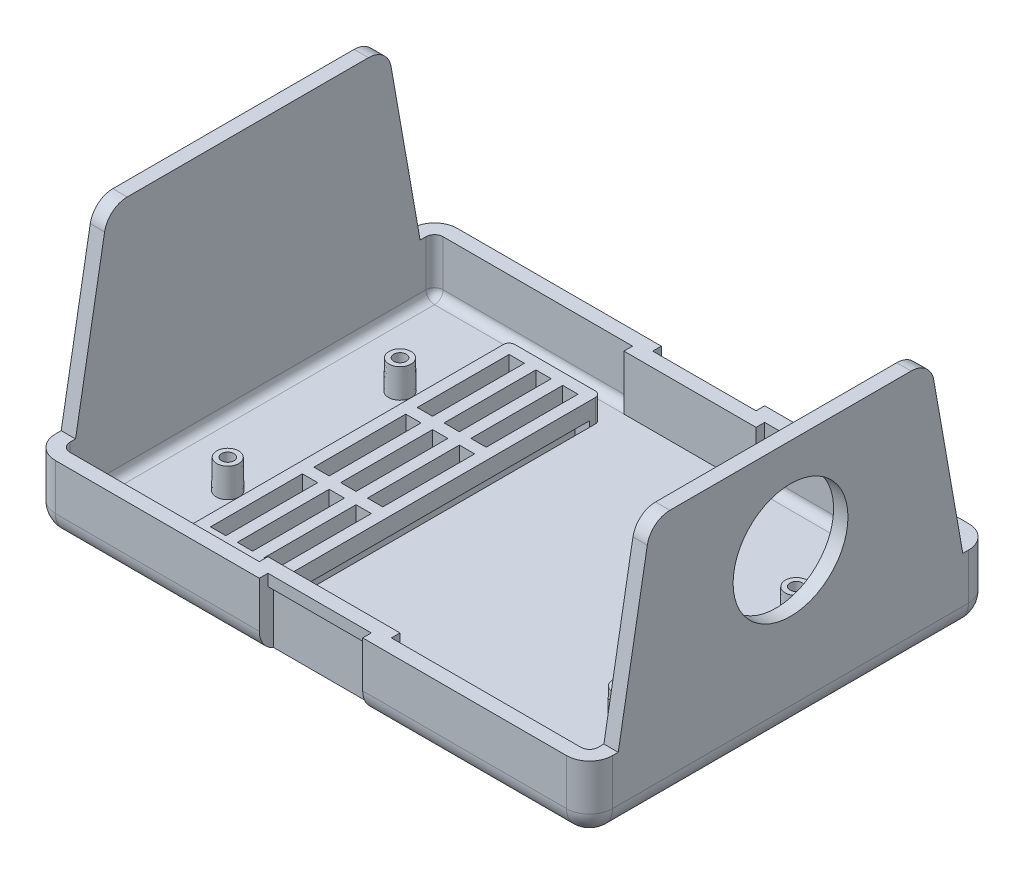
SolidWorks part; units mm, degrees
material "ABS"
ref_plane "Plano frontal" through (0, 0, 0) normal (0, 0, 1) x (1, 0, 0)
ref_plane "Plano superior" through (0, 0, 0) normal (0, 1, 0) x (1, 0, 0)
ref_plane "Plano direito" through (0, 0, 0) normal (1, 0, 0) x (0, 0, -1)
sketch "Esboço1" plane through (0, 0, 0) normal (0, 1, 0) x (1, 0, 0)
  line L0 (-48.5, 35) -> (48.5, -35) construction
  line L1 (-44.5, 35) -> (-9, 35)
  line L2 (-48.5, 31) -> (-48.5, -31)
  line L3 (-44.5, -35) -> (-9, -35)
  line L4 (48.5, 31) -> (48.5, -31)
  line L5 (9, 35) -> (44.5, 35)
  line L6 (9, -35) -> (44.5, -35)
  line L7 (-9, 35) -> (-9, 33.5)
  line L8 (-9, 33.5) -> (9, 33.5)
  line L9 (9, 35) -> (9, 33.5)
  line L11 (9, -35) -> (9, -33.5)
  line L12 (9, -33.5) -> (-9, -33.5)
  line L13 (-9, -35) -> (-9, -33.5)
  arc A0 (-48.5, -31) -> (-44.5, -35) centre (-44.5, -31) ccw
  arc A1 (44.5, -35) -> (48.5, -31) centre (44.5, -31) ccw
  arc A2 (44.5, 35) -> (48.5, 31) centre (44.5, 31) cw
  arc A3 (-44.5, 35) -> (-48.5, 31) centre (-44.5, 31) ccw
  point P7 (-48.5, -35)
  point P13 (48.5, 35)
  dimension "D3" = 4
  dimension "D1" = 97
  dimension "D2" = 70
  dimension "D4" = 1.5
  dimension "D5" = 1.5
  dimension "D6" = 18
  dimension "D7" = 18
  dimension "D8" = 9
  dimension "D9" = 9
extrude "Ressalto-extrusão1" add sketch "Esboço1" along normal blind 44
fillet "Filete1" radius 4 8 edges at (-47.3284, 0, 33.8284) (-48.5, 0, 0) (-47.3284, 0, -33.8284) (-26.75, 0, -35) (47.3284, 0, -33.8284) (48.5, 0, 0) (47.3284, 0, 33.8284) (-26.75, 0, 35)
shell "Casca1" thickness 2.5 removed face at (0, 44, 0)
sketch "Esboço2" plane through (0, 0, 0) normal (1, 0, 0) x (0, 0, -1)
  line L0 (-31, 44) -> (31, 44) construction
  line L1 (-21.0011, 44) -> (21.0011, 44)
  line L2 (-24.9404, 40.6946) -> (-30, 12)
  line L3 (-30, 12) -> (-42.6713, 12)
  line L4 (24.9404, 40.6946) -> (30, 12)
  line L5 (-42.6713, 12) -> (-42.6713, 55.4192)
  line L6 (-42.6713, 55.4192) -> (41.7141, 55.4192)
  line L7 (41.7141, 55.4192) -> (41.7141, 12)
  line L8 (41.7141, 12) -> (30, 12)
  arc A0 (21.0011, 44) -> (24.9404, 40.6946) centre (21.0011, 40) cw
  arc A1 (-21.0011, 44) -> (-24.9404, 40.6946) centre (-21.0011, 40) ccw
  dimension "D1" = 4
  dimension "D2" = 60
  dimension "D3" = 30
extrude "Corte-extrusão1" cut sketch "Esboço2" against normal mid plane 100
sketch "Esboço4" plane through (0, 2.5, 0) normal (0, 1, 0) x (1, 0, 0)
  line L0 (-44.5, 35) -> (-9, 35) construction
  line L1 (-9, -35) -> (-44.5, -35) construction
  line L2 (-48.5, 21.0011) -> (-48.5, -21.0011) construction
  line L3 (48.5, -21.0011) -> (48.5, 21.0011) construction
  circle A0 centre (-34.5, 15) radius 2
  circle A1 centre (-34.5, 15) radius 1
  circle A2 centre (-34.5, -15) radius 2
  circle A3 centre (-34.5, -15) radius 1
  circle A4 centre (34.5, 15) radius 2
  circle A5 centre (34.5, 15) radius 1
  circle A6 centre (34.5, -15) radius 2
  circle A7 centre (34.5, -15) radius 1
  dimension "D5" = 14
  dimension "D7" = 20
  dimension "D8" = 20
  dimension "D9" = 2
  dimension "D10" = 4
  dimension "D11" = 2
  dimension "D12" = 2
  dimension "D13" = 2
  dimension "D1" = 20
  dimension "D2" = 20
  dimension "D3" = 14
  dimension "D4" = 14
  dimension "D6" = 14
extrude "Ressalto-extrusão2" add sketch "Esboço4" along normal blind 5 draft 1 separate body
sketch "Esboço5" plane through (0, 2.5, 0) normal (0, 1, 0) x (1, 0, 0)
  line L0 (-48.5, 21.0011) -> (-48.5, -21.0011) construction
  line L1 (-27.5, -28) -> (-13.5, -28)
  line L2 (-28.5, -27) -> (-28.5, 27)
  line L3 (-27.5, 28) -> (-13.5, 28)
  line L4 (-12.5, -27) -> (-12.5, 27)
  line L6 (-26.5, 26) -> (-23.8333, 26)
  line L7 (-26.5, 26) -> (-26.5, 10)
  line L8 (-26.5, 10) -> (-23.8333, 10)
  line L9 (-23.8333, 26) -> (-23.8333, 10)
  line L10 (-21.8333, 26) -> (-19.1667, 26)
  line L11 (-21.8333, 26) -> (-21.8333, 10)
  line L12 (-21.8333, 10) -> (-19.1667, 10)
  line L13 (-19.1667, 26) -> (-19.1667, 10)
  line L14 (-17.1667, 26) -> (-14.5, 26)
  line L15 (-17.1667, 26) -> (-17.1667, 10)
  line L16 (-17.1667, 10) -> (-14.5, 10)
  line L17 (-14.5, 26) -> (-14.5, 10)
  line L18 (-26.5, 8) -> (-23.8333, 8)
  line L19 (-26.5, 8) -> (-26.5, -8)
  line L20 (-26.5, -8) -> (-23.8333, -8)
  line L21 (-23.8333, 8) -> (-23.8333, -8)
  line L22 (-21.8333, 8) -> (-19.1667, 8)
  line L23 (-21.8333, 8) -> (-21.8333, -8)
  line L24 (-21.8333, -8) -> (-19.1667, -8)
  line L25 (-19.1667, 8) -> (-19.1667, -8)
  line L26 (-17.1667, 8) -> (-14.5, 8)
  line L27 (-17.1667, 8) -> (-17.1667, -8)
  line L28 (-17.1667, -8) -> (-14.5, -8)
  line L29 (-14.5, 8) -> (-14.5, -8)
  line L30 (-26.5, -10) -> (-23.8333, -10)
  line L31 (-26.5, -10) -> (-26.5, -26)
  line L32 (-26.5, -26) -> (-23.8333, -26)
  line L33 (-23.8333, -10) -> (-23.8333, -26)
  line L34 (-21.8333, -10) -> (-19.1667, -10)
  line L35 (-21.8333, -10) -> (-21.8333, -26)
  line L36 (-21.8333, -26) -> (-19.1667, -26)
  line L37 (-19.1667, -10) -> (-19.1667, -26)
  line L38 (-17.1667, -10) -> (-14.5, -10)
  line L39 (-17.1667, -10) -> (-17.1667, -26)
  line L40 (-17.1667, -26) -> (-14.5, -26)
  line L41 (-14.5, -10) -> (-14.5, -26)
  arc A0 (-28.5, 27) -> (-27.5, 28) centre (-27.5, 27) cw
  arc A1 (-13.5, 28) -> (-12.5, 27) centre (-13.5, 27) cw
  arc A2 (-13.5, -28) -> (-12.5, -27) centre (-13.5, -27) ccw
  arc A3 (-27.5, -28) -> (-28.5, -27) centre (-27.5, -27) cw
  point P45 (-28.5, 28)
  point P50 (-12.5, -28)
  point P53 (-28.5, -28)
  dimension "D27" = 1
  dimension "D1" = 56
  dimension "D2" = 16
  dimension "D3" = 20
  dimension "D4" = 28
  dimension "D5" = 16
  dimension "D6" = 2
  dimension "D7" = 2
  dimension "D8" = 2
  dimension "D9" = 2
  dimension "D10" = 16
  dimension "D11" = 2
  dimension "D12" = 2
  dimension "D13" = 2
  dimension "D14" = 16
  dimension "D15" = 2
  dimension "D16" = 2
  dimension "D17" = 2
  dimension "D18" = 16
  dimension "D19" = 16
  dimension "D20" = 16
  dimension "D21" = 2
  dimension "D22" = 2
  dimension "D23" = 16
  dimension "D24" = 16
  dimension "D25" = 2
  dimension "D26" = 2
extrude "Ressalto-extrusão3" add sketch "Esboço5" along normal blind 4
sketch "Esboço6" plane through (-12.5, 0, 0) normal (1, 0, 0) x (0, 0, -1)
  line L1 (-26, 2.5) -> (26, 2.5)
  line L2 (-26, 2.5) -> (-26, 3.5)
  line L3 (-26, 3.5) -> (26, 3.5)
  line L4 (26, 2.5) -> (26, 3.5)
  dimension "D1" = 1
  dimension "D2" = 52
  dimension "D3" = 26
extrude "Corte-extrusão2" cut sketch "Esboço6" against normal blind 16
sketch "Esboço8" plane through (0, 0, 0) normal (0, -1, 0) x (1, 0, 0)
  line L0 (-48.5, -31) -> (-48.5, 31) construction
  line L1 (-28.5, 26) -> (-26, 26)
  line L2 (-28.5, 26) -> (-28.5, -26)
  line L3 (-28.5, -26) -> (-26, -26)
  line L4 (-26, 26) -> (-26, -26)
  line L6 (-24, -26) -> (-21.5, -26)
  line L7 (-24, -26) -> (-24, 26)
  line L8 (-24, 26) -> (-21.5, 26)
  line L9 (-21.5, -26) -> (-21.5, 26)
  line L10 (-19.5, 26) -> (-17, 26)
  line L11 (-19.5, 26) -> (-19.5, -26)
  line L12 (-19.5, -26) -> (-17, -26)
  line L13 (-17, 26) -> (-17, -26)
  line L14 (-15, 26) -> (-12.5, 26)
  line L15 (-15, 26) -> (-15, -26)
  line L16 (-15, -26) -> (-12.5, -26)
  line L17 (-12.5, 26) -> (-12.5, -26)
  dimension "D1" = 52
  dimension "D2" = 2.5
  dimension "D3" = 26
  dimension "D4" = 20
  dimension "D5" = 2
  dimension "D6" = 2
  dimension "D7" = 2.5
  dimension "D8" = 2.5
  dimension "D9" = 2
  dimension "D10" = 2.5
extrude "Corte-extrusão3" cut sketch "Esboço8" against normal blind 2.5
sketch "Esboço9" plane through (0, 0, 33.5) normal (0, 0, 1) x (1, 0, 0)
  line L0 (-9, 12) -> (-9, 0.8775) construction
  line L1 (-9, 10) -> (9, 10)
  line L2 (-9, 10) -> (-9, -1.1849)
  line L3 (-9, -1.1849) -> (9, -1.1849)
  line L4 (9, 10) -> (9, -1.1849)
  line L5 (9, 12) -> (-9, 12) construction
  dimension "D1" = 2
extrude "Corte-extrusão4" cut sketch "Esboço9" against normal blind 1
mirror "Espelhar1" about plane through (0, 0, 0) normal (0, 0, 1) of "Corte-extrusão4"
sketch "Esboço10" plane through (0, 0, 0) normal (1, 0, 0) x (0, 0, -1)
  circle A0 centre (0, 27.5) radius 10
  dimension "D2" = 0
  dimension "D3" = 20
  dimension "D1" = 27.5
extrude "Corte-extrusão5" cut sketch "Esboço10" along normal through all
equation "\"D3@Esboço2\" = \"D2@Esboço2\"/2"
equation "\"D4@Esboço5\" = \"D1@Esboço5\"/2"
equation "\"D3@Esboço6\" = \"D2@Esboço6\"/2"
equation "\"D3@Esboço8\" = \"D1@Esboço8\"/2"
equation "\"D8@Esboço1\" = \"D7@Esboço1\"/2"
equation "\"D9@Esboço1\" = \"D6@Esboço1\"/2"
